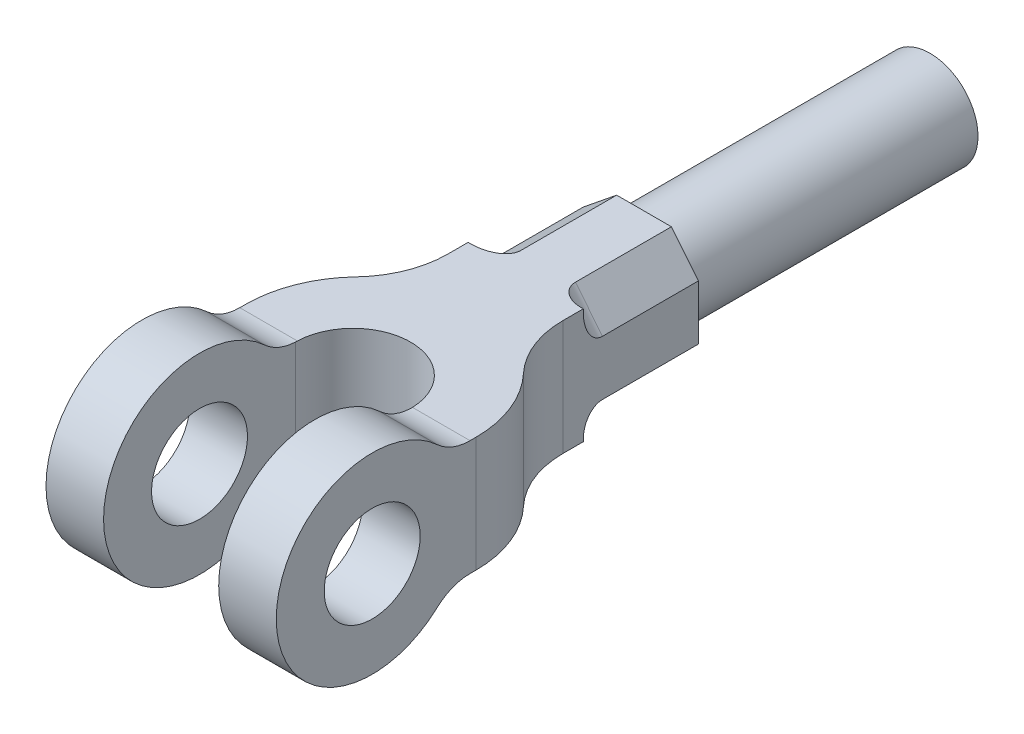
SolidWorks part; units mm, degrees
ref_plane "Front Plane" through (0, 0, 0) normal (0, 0, 1) x (1, 0, 0)
ref_plane "Top Plane" through (0, 0, 0) normal (0, 1, 0) x (1, 0, 0)
ref_plane "Right Plane" through (0, 0, 0) normal (1, 0, 0) x (0, 0, -1)
sketch "Sketch1" plane through (0, 0, 0) normal (0, 1, 0) x (1, 0, 0)
  line L1 (-600, 1250) -> (600, 1250)
  line L2 (-600, 1250) -> (-600, -1250)
  line L3 (-600, -1250) -> (600, -1250)
  line L4 (600, 1250) -> (600, -1250)
  line L5 (-600, 1250) -> (600, -1250) construction
  line L6 (-600, -1250) -> (600, 1250) construction
  point P0 (0, 0)
  dimension "D1" = 1200
  dimension "D2" = 2500
extrude "Boss-Extrude1" add sketch "Sketch1" along normal blind 1000
sketch "Sketch2" plane through (0, 1000, 0) normal (0, 1, 0) x (1, 0, 0)
  line L0 (600, 1250) -> (-600, 1250) construction
  line L1 (0, 1250) -> (0, -1250) construction
  line L2 (-600, -1250) -> (600, -1250) construction
  line L3 (-300, 1250) -> (-300, 544.9834)
  line L4 (300, 1250) -> (300, 544.9834)
  line L5 (-300, -250) -> (-300, -1250)
  line L6 (300, -250) -> (300, -1250)
  line L11 (600, -1250) -> (600, 1250)
  line L12 (600, 1250) -> (-600, 1250)
  line L13 (-600, 1250) -> (-600, -1250)
  line L14 (-600, -1250) -> (600, -1250)
  line L15 (600, -1250) -> (600, 1250)
  line L16 (600, 1250) -> (-600, 1250)
  line L17 (-600, 1250) -> (-600, -1250)
  line L18 (-600, -1250) -> (600, -1250)
  arc A0 (300, -250) -> (-300, -250) centre (0, -250) ccw
  arc A1 (-436.3636, 201.8092) -> (-300, -729.6152) centre (0, -210) ccw
  arc A2 (300, 544.9834) -> (436.3636, 201.8092) centre (800, 544.9834) ccw
  arc A3 (-300, 544.9834) -> (-436.3636, 201.8092) centre (-800, 544.9834) cw
  arc A4 (300, -729.6152) -> (436.3636, 201.8092) centre (0, -210) ccw
  point P6 (0, 1250)
  point P16 (300, 309.6152)
  point P19 (-300, 309.6152)
  line M5 (600, 1250) -> (-600, 1250)
  line M6 (-600, 1250) -> (-600, -1250)
  line M7 (-600, -1250) -> (600, -1250)
  dimension "D1" = 1200
  dimension "D2" = 0
  dimension "D6" = 500
  dimension "D3" = 40
  dimension "D4" = 1500
  dimension "D5" = 300
extrude "Cut-Extrude1" cut sketch "Sketch2" against normal through all contours A3 L3 A1 M5 M6 | A4 L15 L4 A2 M5 | A0 L1 L18 L6 | L1 A0 L5 M7 region at (145.6759, 1000, 630.376) region at (-145.6759, 1000, 630.376) region at (461.7481, 1000, -705.027) region at (-461.7481, 1000, -705.027)
sketch "Sketch3" plane through (600, 0, 0) normal (1, 0, 0) x (0, 0, -1)
  line L0 (201.8092, 0) -> (544.9834, 0) construction
  line L1 (-1250, 1000) -> (-210, 1000) construction
  line L2 (-1250, 1000) -> (-1250, 0) construction
  line L3 (-1250, 0) -> (-210, 0) construction
  line L4 (1250, 0) -> (1250, 1000) construction
  line L5 (1250, 1000) -> (544.9834, 1000) construction
  line L6 (1250, 800) -> (-350, 800)
  line L7 (1250, 800) -> (1250, 200)
  line L8 (1250, 200) -> (-350, 200)
  line L9 (544.9834, 1000) -> (201.8092, 1000) construction
  line L10 (201.8092, 1000) -> (-210, 1000) construction
  line L11 (-210, 0) -> (201.8092, 0) construction
  line L12 (1250, 0) -> (544.9834, 0) construction
  line L13 (1250, 1000) -> (544.9834, 1000)
  line L14 (544.9834, 1000) -> (201.8092, 1000)
  line L15 (201.8092, 1000) -> (-210, 1000)
  line L16 (-1250, 1000) -> (-210, 1000)
  line L17 (-1250, 1000) -> (-1250, 0)
  line L18 (-1250, 0) -> (-210, 0)
  line L19 (-210, 0) -> (201.8092, 0)
  line L20 (201.8092, 0) -> (544.9834, 0)
  line L21 (1250, 0) -> (544.9834, 0)
  line L22 (1250, 0) -> (1250, 1000)
  arc A0 (-350, 800) -> (-350, 200) centre (-750, 500) ccw
  circle A1 centre (-750, 500) radius 250
  line M3 (-1250, 0) -> (-210, 0)
  line M4 (-210, 0) -> (-210, 1000)
  line M5 (-210, 1000) -> (-1250, 1000)
  line M6 (-1250, 1000) -> (-1250, 0)
  dimension "D1" = 500
  dimension "D2" = 600
extrude "Cut-Extrude2" cut sketch "Sketch3" against normal through all contours A0 L16 M6 | A0 L6 M4 M5 | L6 L22 L13 L14 L15 M4 | L21 L22 L8 L19 L20 M4 | A0 L18 L8 M4 | A0 L17 M3 | A1 region at (600, 900, -520) region at (600, 919.8016, 356.564) region at (600, 100, -520) region at (600, 80.1984, 356.564) region at (600, 888.316, 1138.316) region at (600, 111.684, 1138.316) region at (600, 500, 750)
fillet "Fillet1" radius 250 4 edges at (-450, 200, 350) (450, 200, 350) (-450, 800, 350) (450, 800, 350)
sketch "Sketch4" plane through (0, 0, -1250) normal (0, 0, -1) x (-1, 0, 0)
  line L0 (300, 800) -> (-300, 200) construction
  line L1 (126, 800) -> (300, 800)
  line L2 (300, 800) -> (-300, 800) construction
  line L3 (300, 800) -> (300, 659.3238)
  line L4 (300, 200) -> (300, 800) construction
  line L5 (300, 659.3238) -> (126, 800)
  line L6 (126, 800) -> (119.9556, 800.7624)
  line L7 (300, 374) -> (300, 200)
  line L8 (159.3238, 200) -> (300, 374)
  line L9 (300, 200) -> (159.3238, 200)
  line L10 (-126, 200) -> (-300, 200)
  line L11 (-300, 340.6762) -> (-126, 200)
  line L12 (-300, 200) -> (-300, 340.6762)
  line L13 (-300, 626) -> (-300, 800)
  line L14 (-159.3238, 800) -> (-300, 626)
  line L15 (-300, 800) -> (-159.3238, 800)
  circle A0 centre (0, 500) radius 250
  point P25 (0, 500)
  line M3 (-300, 800) -> (-300, 200)
  line M4 (-300, 200) -> (300, 200)
  line M5 (300, 200) -> (300, 800)
  line M6 (300, 800) -> (-300, 800)
  dimension "D1" = 500
  dimension "D2" = 174
  dimension "D3" = 140.6762
  dimension "D4" = 4
extrude "Cut-Extrude3" cut sketch "Sketch4" against normal blind 600 contours L14 M6 M3 | L0 L5 M5 | L0 L5 M6 | L8 M4 M5 | L11 L0 M4 | L0 L11 M3 region at (-274.0711, 727.179, -1250) region at (-216.0711, 774.0711, -1250) region at (253.1079, 742, -1250) region at (-253.1079, 258, -1250) region at (216.0711, 225.9289, -1250) region at (274.0711, 272.821, -1250)
extrude "Boss-Extrude2" add sketch "Sketch4<3>" along normal blind 1507 contours A0 L0 | L0 A0 region at (-75.0264, 424.9736, -1250) region at (75.0264, 575.0264, -1250)
sketch "Sketch4<3>" plane through (0, 0, -1250) normal (0, 0, -1) x (-1, 0, 0) same geometry as "Sketch4"
fillet "Fillet6" radius 100 1 edges at (-213, 729.6619, -650)
fillet "Fillet7" radius 100 3 edges at (229.6619, 713, -650) (213, 270.3381, -650) (-229.6619, 287, -650)
